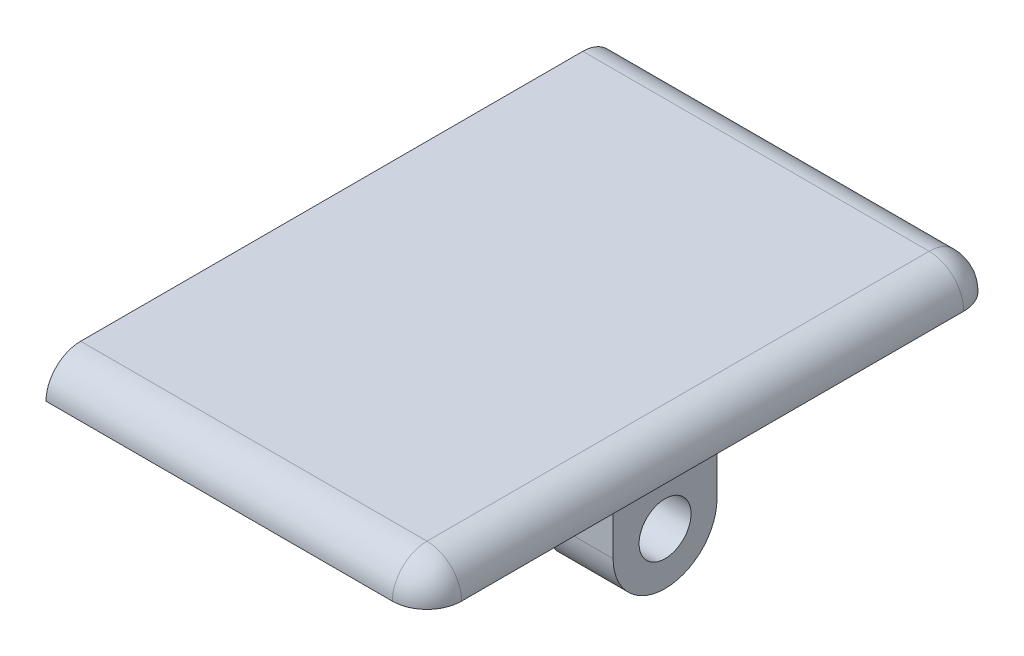
SolidWorks part; units mm, degrees
ref_plane "Front Plane" through (0, 0, 0) normal (0, 0, 1) x (1, 0, 0)
ref_plane "Top Plane" through (0, 0, 0) normal (0, 1, 0) x (1, 0, 0)
ref_plane "Right Plane" through (0, 0, 0) normal (1, 0, 0) x (0, 0, -1)
sketch "Sketch1" plane through (0, 0, 0) normal (0, 1, 0) x (1, 0, 0)
  line L1 (-19.25, 28.25) -> (-0.75, 28.25)
  line L2 (-19.25, 28.25) -> (-19.25, 0.75)
  line L3 (-19.25, 0.75) -> (-0.75, 0.75)
  line L4 (-0.75, 28.25) -> (-0.75, 0.75)
  line L5 (0, 29) -> (-20, 29) construction
  line L6 (0, 29) -> (0, 0) construction
  line L7 (0, 0) -> (-20, 0) construction
  line L8 (-20, 29) -> (-20, 0) construction
  dimension "D1" = 0.75
  dimension "D2" = 0.75
  dimension "D3" = 0.75
  dimension "D4" = 0.75
extrude "Boss-Extrude1" add sketch "Sketch1" against normal blind 2
sketch "Sketch3" plane through (-0.75, 0, 0) normal (1, 0, 0) x (0, 0, -1)
  line L0 (0.75, -2) -> (28.25, -2) construction
  line L1 (11.5, -5) -> (11.5, -2)
  line L2 (11.5, -2) -> (17.5, -2)
  line L3 (17.5, -2) -> (17.5, -5)
  circle A0 centre (14.5, -5) radius 3 construction
  arc A1 (11.5, -5) -> (17.5, -5) centre (14.5, -5) ccw
  circle A2 centre (14.5, -5) radius 1.5
  point P4 (14.5, -2)
  dimension "D1" = 6
  dimension "D2" = 3
extrude "Boss-Extrude2" add sketch "Sketch3" against normal blind 4
sketch "Sketch4" plane through (0, 0, 0) normal (0, 1, 0) x (1, 0, 0)
  line L0 (0, -2) -> (-20, -2) construction
  line L1 (0, -2) -> (-20, -2)
  line L2 (2, 29) -> (2, 0) construction
  line L3 (2, 29) -> (2, 0)
  line L4 (0, 31) -> (-20, 31) construction
  line L5 (0, 31) -> (-20, 31)
  line L6 (-20, -2) -> (-20, 31)
  arc A0 (0, -2) -> (2, 0) centre (0, 0) ccw construction
  arc A1 (0, -2) -> (2, 0) centre (0, 0) ccw
  arc A2 (2, 29) -> (0, 31) centre (0, 29) ccw construction
  arc A3 (2, 29) -> (0, 31) centre (0, 29) ccw
extrude "Boss-Extrude3" add sketch "Sketch4" along normal blind 2
fillet "Fillet1" radius 2 5 edges at (-10, 2, -31) (1.4142, 2, -30.4142) (2, 2, -14.5) (1.4142, 2, 1.4142) (-10, 2, 2)
